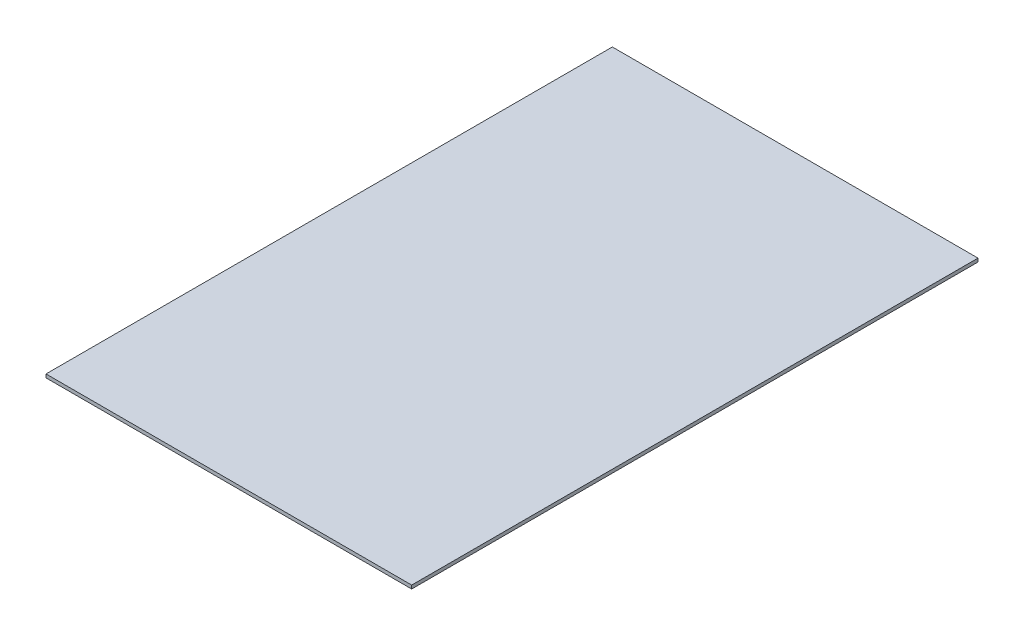
SolidWorks part; units mm, degrees
ref_plane "前视基准面" through (0, 0, 0) normal (0, 0, 1) x (1, 0, 0)
ref_plane "上视基准面" through (0, 0, 0) normal (0, 1, 0) x (1, 0, 0)
ref_plane "右视基准面" through (0, 0, 0) normal (1, 0, 0) x (0, 0, -1)
other "Configuration Table"
sketch "草图1" plane through (0, 0, 0) normal (0, 1, 0) x (1, 0, 0)
  line L1 (-159.28, 246.665) -> (159.28, 246.665)
  line L2 (-159.28, 246.665) -> (-159.28, -246.665)
  line L3 (-159.28, -246.665) -> (159.28, -246.665)
  line L4 (159.28, 246.665) -> (159.28, -246.665)
  line L5 (-159.28, 246.665) -> (159.28, -246.665) construction
  line L6 (-159.28, -246.665) -> (159.28, 246.665) construction
  point P0 (0, 0)
  dimension "D1" = 318.56
  dimension "D2" = 493.33
extrude "凸台-拉伸1" add sketch "草图1" along normal blind 3
